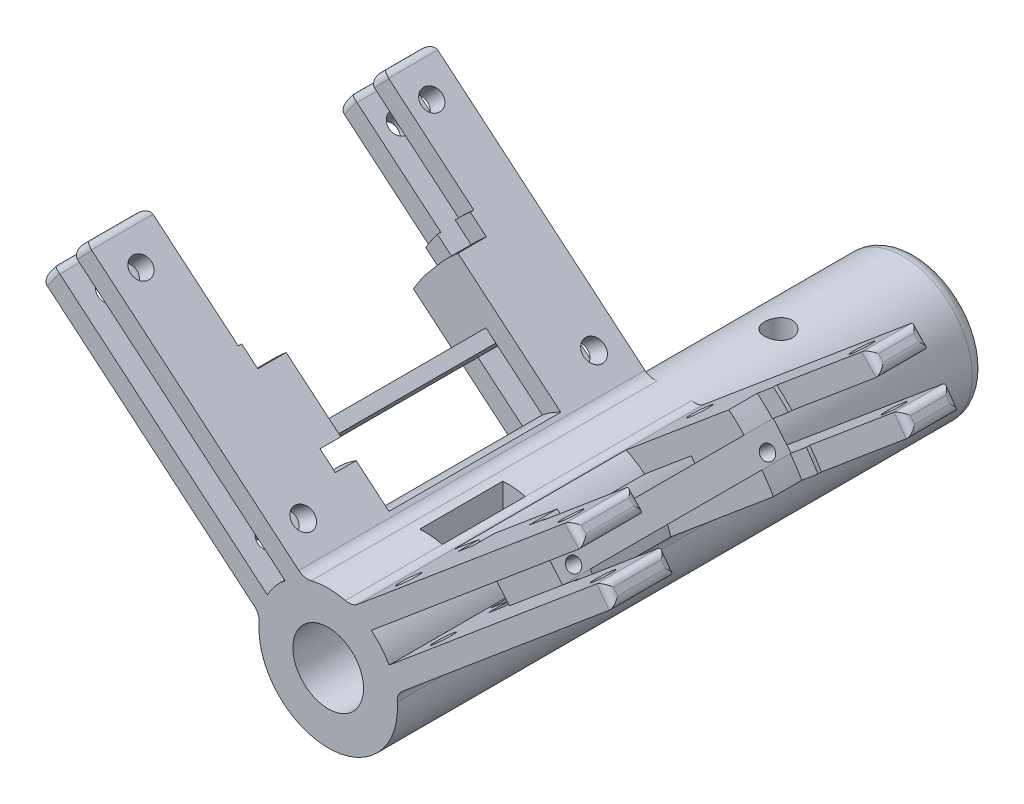
SolidWorks part; units mm, degrees
ref_plane "前视基准面" through (0, 0, 0) normal (0, 0, 1) x (1, 0, 0)
ref_plane "上视基准面" through (0, 0, 0) normal (0, 1, 0) x (1, 0, 0)
ref_plane "右视基准面" through (0, 0, 0) normal (1, 0, 0) x (0, 0, -1)
other "Configuration Table"
sketch "草图1" plane through (0, 0, 0) normal (0, 0, 1) x (1, 0, 0)
  circle A0 centre (0, 0) radius 5.1
  circle A1 centre (0, 0) radius 10
  dimension "D1" = 10.2
  dimension "D2" = 20
extrude "凸台-拉伸1" add sketch "草图1" along normal blind 35
sketch "草图2" plane through (0, 0, 35) normal (0, 0, 1) x (1, 0, 0)
  line L0 (0, -50) -> (0, 50) construction
  line L6 (-38.3022, -32.1394) -> (38.3022, 32.1394) construction
  line L7 (36.986, 33.6457) -> (6.2201, 7.8301)
  line L8 (3.4202, 9.3969) -> (34.8963, 35.8085)
  line L9 (34.8963, 35.8085) -> (36.986, 33.6457)
  line L10 (41.3242, 28.1481) -> (39.5571, 30.5816)
  line L11 (39.5571, 30.5816) -> (8.7912, 4.7659)
  line L12 (9.8481, 1.7365) -> (41.3242, 28.1481)
  line L13 (-41.3242, 28.1481) -> (-39.5571, 30.5816)
  line L14 (-34.8963, 35.8085) -> (-36.986, 33.6457)
  line L15 (-9.8481, 1.7365) -> (-41.3242, 28.1481)
  line L16 (-39.5571, 30.5816) -> (-8.7912, 4.7659)
  line L17 (-36.986, 33.6457) -> (-6.2201, 7.8301)
  line L18 (-3.4202, 9.3969) -> (-34.8963, 35.8085)
  circle A0 centre (0, 0) radius 50 construction
  circle A1 centre (0, 0) radius 5.1
  circle A2 centre (0, 0) radius 10 construction
  circle M16 centre (0, 0) radius 10
  circle M17 centre (0, 0) radius 5.1
  dimension "60" = 100
  dimension "D6" = 10.2
  dimension "D1" = 50
  dimension "D4" = 2
  dimension "D5" = 3
extrude "凸台-拉伸2" add sketch "草图2" along normal blind 50 contours M16 M17 | L12 L10 L11 M16 | L9 L8 L7 M16 | L18 L14 L17 M16 | L16 L13 L15 M16 region at (20.4114, 21.7036, 35) region at (7.4438, 6.2461, 35) region at (24.9182, 16.3325, 35) region at (-20.4114, 21.7036, 35) region at (-24.9182, 16.3325, 35)
fillet "圆角2" radius 2 4 edges at (9.8481, 1.7365, 60) (3.4202, 9.3969, 60) (-3.4202, 9.3969, 60) (-9.8481, 1.7365, 60)
fillet "圆角3" radius 2 1 edges at (10, 0, 0)
sketch "草图3" plane through (0, 0, 0) normal (0, 1, 0) x (1, 0, 0)
  line L0 (2.4725, -85) -> (2.4725, -35) construction
  line L1 (-0.8012, -58.9922) -> (2.4725, -58.9922)
  line L2 (-0.8012, -58.9922) -> (-0.8012, -70.9922)
  line L3 (-0.8012, -70.9922) -> (2.4725, -70.9922)
  line L4 (2.4725, -58.9922) -> (2.4725, -70.9922)
  line L5 (-0.8012, -58.9922) -> (2.4725, -70.9922) construction
  line L6 (-0.8012, -70.9922) -> (2.4725, -58.9922) construction
  circle A0 centre (0, -20) radius 2
  point P4 (0.8356, -64.9922)
  dimension "D2" = 4
  dimension "D1" = 20
  dimension "D3" = 3.2737
  dimension "D4" = 12
  dimension "D5" = 45
extrude "切除-拉伸2" cut sketch "草图3" along normal through all
ref_plane "基准面2" through (0, 0, 0) normal (-0.6428, 0.766, 0) x (0.766, 0.6428, 0)
sketch "草图12" plane through (0, 0, 0) normal (-0.6428, 0.766, 0) x (0.766, 0.6428, 0)
  line L0 (10, -85) -> (10, -2) construction
  line L5 (14.997, -39) -> (44.997, -39) construction
  line L6 (9.7468, -35) -> (49.7494, -35) construction
  line L7 (14.997, -39) -> (14.997, -81) construction
  line L12 (9.7468, -85) -> (49.7494, -85) construction
  line L19 (29.65, -42.1) -> (50, -42.1)
  line L35 (11, -46.2) -> (29.65, -46.2)
  line L36 (29.65, -42.1) -> (29.65, -46.2)
  line L37 (33.15, -42.1) -> (29.65, -42.1)
  line L38 (33.15, -42.1) -> (33.15, -46.2)
  line L39 (33.15, -46.2) -> (34.65, -46.2)
  line L40 (34.65, -46.2) -> (34.65, -54.5)
  line L41 (34.65, -54.5) -> (38.45, -54.5)
  line L42 (38.45, -60.9725) -> (38.45, -54.5)
  line L43 (38.45, -60.9725) -> (43.45, -60.9725)
  line L45 (38.45, -67.7275) -> (43.45, -67.7275)
  line L46 (38.45, -72) -> (38.45, -67.7275)
  line L47 (33.15, -72) -> (38.45, -72)
  line L48 (33.15, -76.1) -> (33.15, -72)
  line L49 (29.65, -76.1) -> (33.15, -76.1)
  line L50 (29.65, -76.1) -> (29.65, -72)
  line L51 (11, -72) -> (29.65, -72)
  line L52 (11, -46.2) -> (11, -72)
  line L53 (0, 0) -> (0, -20) construction
  line L54 (11.5, -46.7) -> (30.15, -46.7)
  line L55 (30.15, -42.6) -> (30.15, -46.7)
  line L56 (32.65, -42.6) -> (30.15, -42.6)
  line L57 (32.65, -42.6) -> (32.65, -46.7)
  line L58 (32.65, -46.7) -> (34.15, -46.7)
  line L59 (34.15, -46.7) -> (34.15, -55)
  line L60 (34.15, -55) -> (37.95, -55)
  line L61 (37.95, -61.4725) -> (37.95, -55)
  line L62 (37.95, -61.4725) -> (42.95, -61.4725)
  line L63 (42.95, -61.4725) -> (42.95, -67.2275)
  line L64 (37.95, -67.2275) -> (42.95, -67.2275)
  line L65 (37.95, -71.5) -> (37.95, -67.2275)
  line L66 (32.65, -71.5) -> (37.95, -71.5)
  line L67 (32.65, -75.6) -> (32.65, -71.5)
  line L68 (30.15, -75.6) -> (32.65, -75.6)
  line L69 (30.15, -75.6) -> (30.15, -71.5)
  line L70 (11.5, -71.5) -> (30.15, -71.5)
  line L71 (11.5, -46.7) -> (11.5, -71.5)
  line L72 (43.45, -60.9725) -> (43.45, -67.7275) construction
  line L73 (43.45, -60.9725) -> (43.45, -67.7275)
  line L75 (50, -42.1) -> (50, -76.1)
  line L76 (50, -76.1) -> (29.65, -76.1)
  line L78 (32.65, -42.6) -> (33.15, -42.6)
  line L79 (32.65, -75.6) -> (33.15, -75.6)
  circle A8 centre (14.997, -39) radius 1.5
  circle A9 centre (44.997, -39) radius 1.5
  circle A10 centre (44.997, -81) radius 1.5
  circle A11 centre (14.997, -81) radius 1.5
  dimension "D6" = 4.997
  dimension "D4" = 3
  dimension "D2" = 20
  dimension "D3" = 5
  dimension "D5" = 4
  dimension "D8" = 30
  dimension "D9" = 4
  dimension "D10" = 2
  dimension "D7" = 90
  dimension "D1" = 0.5
  dimension "D11" = 2
revolve "切除-旋转3" cut sketch "草图12" angle 360 about L53
ref_plane "基准面3" through (0, 0, 75.5) normal (0, 0, 1) x (1, 0, 0)
sketch "草图16" plane through (0, 0, 75.5) normal (0, 0, 1) x (1, 0, 0)
  line L0 (14.0993, 14.4416) -> (21.7598, 20.8694)
  line L3 (21.7598, 20.8694) -> (24.3309, 17.8053)
  line L5 (24.3309, 17.8053) -> (16.6705, 11.3774)
  line L6 (0, 0) -> (0, 4.0927) construction
  line L7 (-14.0993, 14.4416) -> (-16.6705, 11.3774)
  line L8 (-24.3309, 17.8053) -> (-16.6705, 11.3774)
  line L9 (-21.7598, 20.8694) -> (-24.3309, 17.8053)
  line L10 (36.986, 33.6457) -> (6.2201, 7.8301) construction
  line L11 (39.5571, 30.5816) -> (8.7912, 4.7659) construction
  line L12 (14.0993, 14.4416) -> (16.6705, 11.3774)
  line L13 (-14.0993, 14.4416) -> (-21.7598, 20.8694)
  arc A1 (25.9904, 15.2815) -> (24.3309, 17.8053) centre (0, 0) ccw construction
  dimension "D1" = 10
extrude "凸台-拉伸3" add sketch "草图16" against normal blind 33 contours L5 L3 L0 | L7 L13 L9 L8 region at (19.2151, 16.1234, 75.5) region at (-19.2151, 16.1234, 75.5)
sketch "草图20" plane through (23.0454, 19.3374, 0) normal (0.766, 0.6428, 0) x (0, 0, -1)
  circle A0 centre (-73.1, -0.75) radius 1
  circle A1 centre (-45.1, -0.75) radius 1
  dimension "D1" = 2
  dimension "D2" = 2
extrude "切除-拉伸3" cut sketch "草图20" against normal blind 5
sketch "草图21" plane through (-23.0454, 19.3374, 0) normal (-0.766, 0.6428, 0) x (0, 0, 1)
  circle A0 centre (73.1, -0.75) radius 1
  circle A1 centre (45.1, -0.75) radius 1
  dimension "D1" = 2
  dimension "D2" = 2
extrude "切除-拉伸4" cut sketch "草图21" against normal blind 5
fillet "圆角5" radius 1 32 edges at (-40.4407, 29.3648, 76.1) (-39.5571, 30.5816, 80.55) (-41.3242, 28.1481, 80.55) (-35.9411, 34.7271, 76.1) (-34.8963, 35.8085, 80.55) (-36.986, 33.6457, 80.55) (-41.3242, 28.1481, 38.55) (-40.4407, 29.3648, 35) (-39.5571, 30.5816, 38.55) (-40.4407, 29.3648, 42.1) (-35.9411, 34.7271, 35) (-34.8963, 35.8085, 38.55) (-35.9411, 34.7271, 42.1) (-36.986, 33.6457, 38.55) (35.9411, 34.7271, 76.1) (36.986, 33.6457, 80.55) (34.8963, 35.8085, 80.55) (40.4407, 29.3648, 76.1) (41.3242, 28.1481, 80.55) (39.5571, 30.5816, 80.55) (40.4407, 29.3648, 35) (41.3242, 28.1481, 38.55) (40.4407, 29.3648, 42.1) (39.5571, 30.5816, 38.55) (34.8963, 35.8085, 38.55) (35.9411, 34.7271, 35) (36.986, 33.6457, 38.55) (35.9411, 34.7271, 42.1) (35.9411, 34.7271, 85) (-40.4407, 29.3648, 85) (-35.9411, 34.7271, 85) (40.4407, 29.3648, 85)
sketch "草图22" plane through (-1.2856, 1.5321, 0) normal (-0.6428, 0.766, 0) x (0.766, 0.6428, 0)
  line L0 (29.7325, -71.5) -> (10.3562, -71.5) construction
  line L1 (30.0836, -46.7) -> (20.0443, -46.7)
  line L2 (30.0836, -46.7) -> (30.0836, -71.5)
  line L3 (30.0836, -71.5) -> (20.0443, -71.5)
  line L4 (20.0443, -46.7) -> (20.0443, -71.5)
  line L5 (30.0836, -42.6) -> (30.0836, -46.7) construction
  line L10 (29.7325, -46.7) -> (10.3562, -46.7) construction
  line L11 (0, 0) -> (0, -23.6618) construction
  line L12 (8, 0) -> (-8, 0) construction
  line L13 (20.0836, -71.5) -> (20.0836, -75.5) construction
  line L14 (18.0836, -71.5) -> (15.2973, -71.5)
  line L15 (18.0836, -71.5) -> (18.0836, -74.5)
  line L16 (18.0836, -74.5) -> (15.2973, -74.5)
  line L17 (15.2973, -71.5) -> (15.2973, -74.5)
  dimension "D1" = 3
  dimension "D2" = 2.7863
  dimension "D3" = 2
revolve "切除-旋转5" cut sketch "草图22" angle 360 about L11
